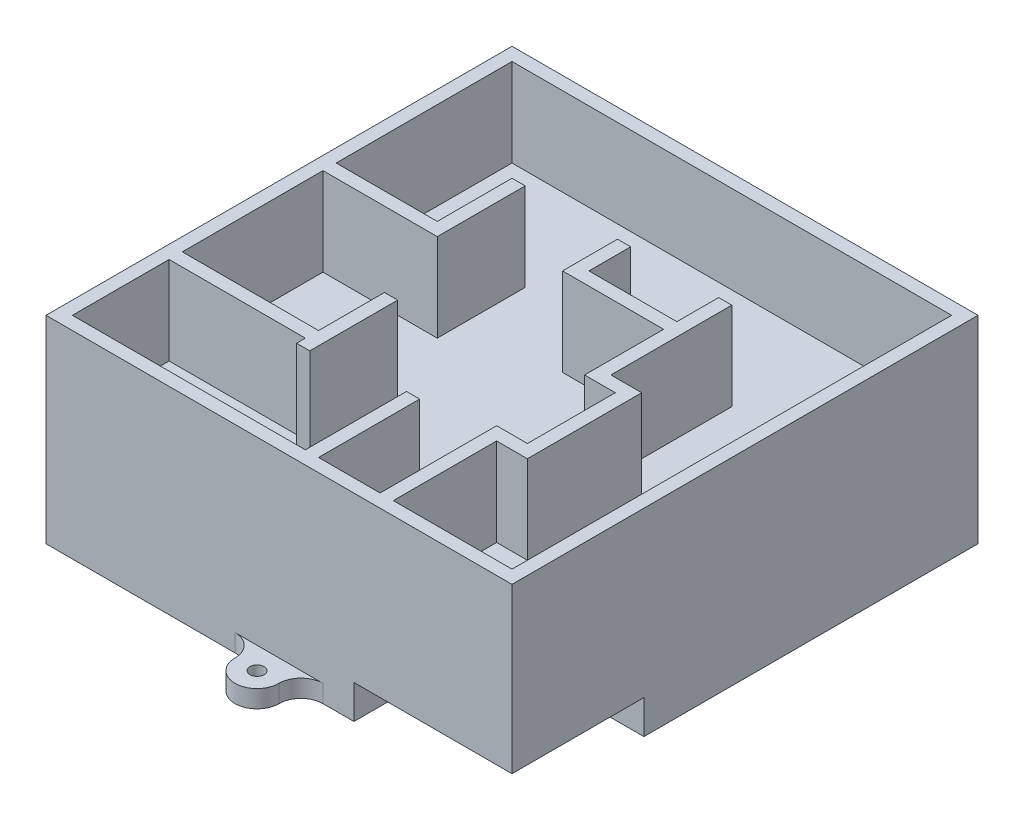
SolidWorks part; units mm, degrees
ref_plane "Front Plane" through (0, 0, 0) normal (0, 0, 1) x (1, 0, 0)
ref_plane "Top Plane" through (0, 0, 0) normal (0, 1, 0) x (1, 0, 0)
ref_plane "Right Plane" through (0, 0, 0) normal (1, 0, 0) x (0, 0, -1)
sketch "Sketch2" plane through (0, 0, 0) normal (0, 1, 0) x (1, 0, 0)
  line L1 (0, 0) -> (106, 0)
  line L2 (0, 0) -> (0, 106)
  line L3 (0, 106) -> (106, 106)
  line L4 (106, 0) -> (106, 106)
  circle A0 centre (18, 15) radius 4
  circle A1 centre (92, 13.5) radius 6
  dimension "D3" = 8
  dimension "D4" = 12
  dimension "D5" = 15
  dimension "D6" = 18
  dimension "D7" = 13.5
  dimension "D8" = 14
  dimension "D1" = 106
  dimension "D2" = 106
extrude "Boss-Extrude1" add sketch "Sketch2" along normal blind 25
sketch "Sketch3" plane through (0, 25, 0) normal (0, 1, 0) x (1, 0, 0)
  line L0 (3, 103) -> (3, 3)
  line L1 (0, 106) -> (106, 106)
  line L2 (0, 106) -> (0, 0)
  line L3 (0, 0) -> (106, 0)
  line L4 (106, 106) -> (106, 0)
  line L5 (3, 3) -> (103, 3)
  line L6 (103, 103) -> (103, 3)
  line L7 (3, 103) -> (103, 103)
  dimension "D1" = 3
extrude "Boss-Extrude2" add sketch "Sketch3" along normal blind 20
sketch "Sketch5" plane through (0, 25, 0) normal (0, 1, 0) x (1, 0, 0)
  line L2 (3, 28) -> (3, 25)
  line L5 (3, 103) -> (3, 3) construction
  line L6 (83, 52.5) -> (83, 26.5)
  line L9 (34, 43) -> (37, 43)
  line L10 (37, 23) -> (37, 43)
  line L12 (3, 63) -> (3, 60)
  line L19 (26, 63) -> (26, 80)
  line L20 (3, 3) -> (103, 3) construction
  line L21 (56, 3) -> (59, 3)
  line L22 (56, 3) -> (56, 26)
  line L23 (56, 26) -> (59, 26)
  line L24 (59, 3) -> (59, 26)
  line L25 (3, 28) -> (34, 28)
  line L26 (3, 3) -> (103, 3) construction
  line L27 (73, 3) -> (76, 3)
  line L30 (76, 3) -> (76, 26.5)
  line L38 (80, 29.5) -> (80, 49.5)
  line L41 (80, 49.5) -> (73, 49.5)
  line L42 (73, 52.5) -> (73, 49.5)
  line L44 (76, 26.5) -> (83, 26.5)
  line L45 (73, 52.5) -> (83, 52.5)
  line L47 (3, 63) -> (26, 63)
  line L50 (80, 29.5) -> (73, 29.5)
  line L51 (73, 29.5) -> (73, 3)
  line L52 (29, 60) -> (3, 60)
  line L53 (29, 60) -> (29, 80)
  line L54 (29, 80) -> (26, 80)
  line L55 (34, 43) -> (34, 28)
  line L56 (3, 25) -> (34, 25)
  line L57 (34, 25) -> (34, 23)
  line L58 (34, 23) -> (37, 23)
  dimension "D1" = 31
  dimension "D2" = 31
  dimension "D3" = 0
extrude "Boss-Extrude3" add sketch "Sketch5" along normal blind 20 contours L9 L10 L58 L57 L56 L2 L25 L55 | L54 L19 L47 L12 L52 L53 | L22 L21 L24 L23 | L51 L27 L30 L44 L6 L45 L42 L41 L38 L50
sketch "Sketch7" plane through (0, 25, 0) normal (0, 1, 0) x (1, 0, 0)
  line L1 (73, 52.5) -> (76, 52.5)
  line L2 (73, 52.5) -> (73, 80)
  line L3 (73, 80) -> (76, 80)
  line L4 (76, 52.5) -> (76, 80)
  line L5 (73, 70.4965) -> (53, 70.4965)
  line L6 (73, 70.4965) -> (73, 67.4965)
  line L7 (73, 67.4965) -> (53, 67.4965)
  line L8 (53, 70.4965) -> (53, 67.4965)
  line L9 (53, 67.4965) -> (50, 67.4965)
  line L10 (53, 67.4965) -> (53, 79.9965)
  line L11 (53, 79.9965) -> (50, 79.9965)
  line L12 (50, 67.4965) -> (50, 79.9965)
  line M14 (73, 52.5) -> (83, 52.5)
  dimension "D1" = 3
  dimension "D2" = 3
  dimension "D3" = 3
  dimension "D4" = 27.5
  dimension "D5" = 20
  dimension "D6" = 12.5
  dimension "D7" = 9.5035
extrude "Boss-Extrude4" add sketch "Sketch7" along normal blind 20 contours L12 L9 L8 L10 L11 | L5 L8 L7 L2 | L4 L3 L2 M14 region at (74.5, 25, -66.25) region at (63, 25, -68.9965) region at (51.5, 25, -73.7465)
sketch "Sketch10" plane through (0, 0, 0) normal (0, 0, 1) x (1, 0, 0)
  line L0 (0, 0) -> (106, 0) construction
  line L1 (48, 4) -> (58, 4)
  line L2 (48, 4) -> (48, 0)
  line L3 (48, 0) -> (58, 0)
  line L4 (58, 4) -> (58, 0)
  line L5 (0, 45) -> (106, 45) construction
  point P6 (53, 4)
  point P9 (53, 45)
  dimension "D1" = 10
  dimension "D2" = 4
  dimension "D3" = 0
  dimension "D4" = 0
extrude "Boss-Extrude5" add sketch "Sketch10" along normal blind 10
sketch "Sketch11" plane through (0, 0, -106) normal (0, 0, -1) x (-1, 0, 0)
  line L0 (-106, 45) -> (0, 45) construction
  line L1 (-58, 4) -> (-48, 4)
  line L2 (-58, 4) -> (-58, 0)
  line L3 (-58, 0) -> (-48, 0)
  line L4 (-48, 4) -> (-48, 0)
  line L5 (-106, 0) -> (0, 0) construction
  point P4 (-53, 4)
  point P7 (-53, 45)
  dimension "D1" = 10
  dimension "D2" = 4
  dimension "D3" = 0
  dimension "D4" = 0
extrude "Boss-Extrude6" add sketch "Sketch11" along normal blind 10
fillet "Fillet2" 2 edges at (48, 2, -116) (58, 2, -116) type full round first side face at (48, 2, -111) second side face at (58, 2, -111) middle face at (53, 2, -116)
fillet "Fillet3" radius 5 2 edges at (48, 2, -106) (58, 2, -106)
fillet "Fillet4" radius 5 2 edges at (48, 2, 0) (58, 2, 0)
fillet "Fillet5" 2 edges at (48, 2, 10) (58, 2, 10) type full round first side face at (48, 2, 7.5) second side face at (58, 2, 7.5) middle face at (53, 2, 10)
sketch "Sketch13" plane through (0, 4, 0) normal (0, 1, 0) x (1, 0, 0)
  circle A0 centre (53, -5) radius 1.6
  circle A1 centre (53, 111) radius 1.6
  dimension "D1" = 3.2
  dimension "D2" = 3.2
extrude "Cut-Extrude2" cut sketch "Sketch13" against normal through all
sketch "Sketch14" plane through (0, 0, 0) normal (0, 0, 1) x (1, 0, 0)
  line L1 (106, 0) -> (70.0395, 0)
  line L2 (106, 0) -> (106, 7.6935)
  line L3 (106, 7.6935) -> (70.0395, 7.6935)
  line L4 (70.0395, 0) -> (70.0395, 7.6935)
extrude "Cut-Extrude3" cut sketch "Sketch14" against normal blind 30
